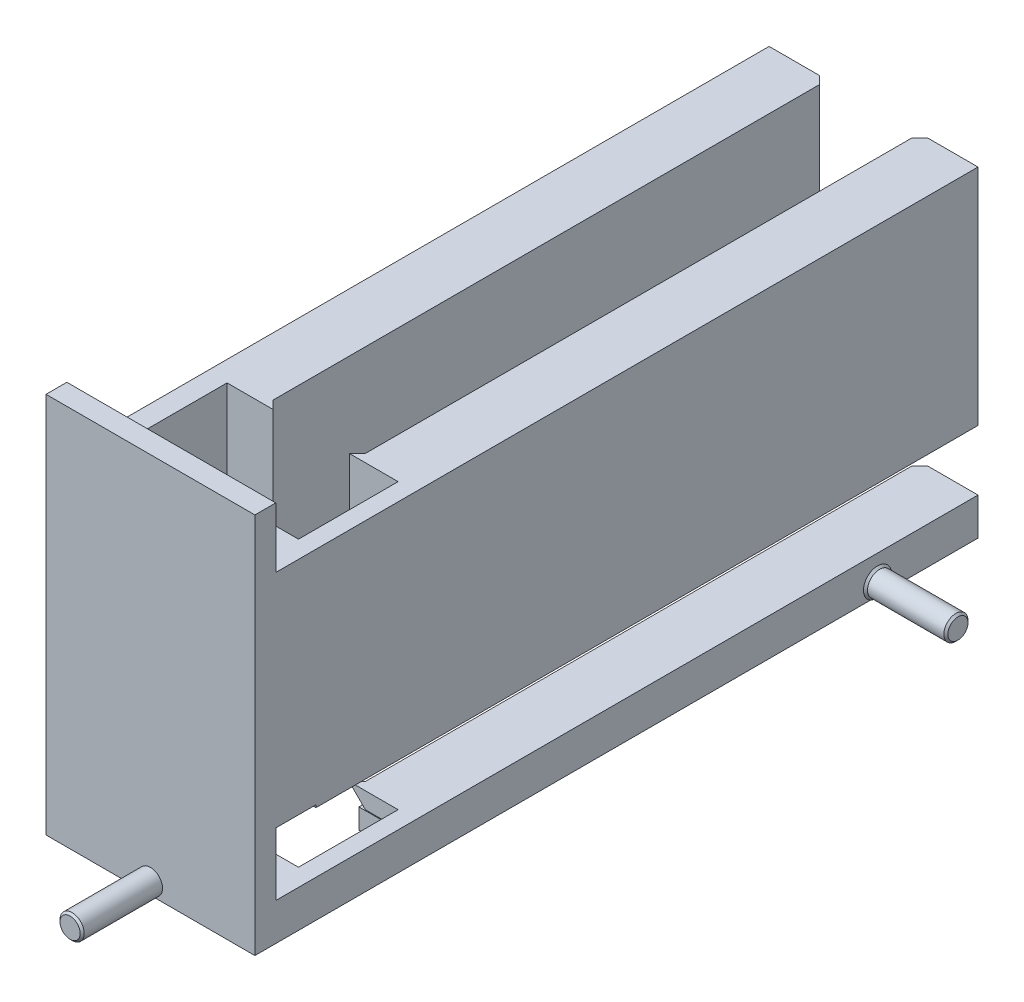
SolidWorks part; units mm, degrees
ref_plane "前视基准面" through (0, 0, 0) normal (0, 0, 1) x (1, 0, 0)
ref_plane "上视基准面" through (0, 0, 0) normal (0, 1, 0) x (1, 0, 0)
ref_plane "右视基准面" through (0, 0, 0) normal (1, 0, 0) x (0, 0, -1)
sketch "草图1" plane through (0, 0, 0) normal (0, 0, 1) x (1, 0, 0)
  line L0 (0, 0) -> (0, 95) construction
  line L1 (-21, 0) -> (21, 0) construction
  line L2 (21, 0) -> (21, 95) construction
  line L3 (21, 95) -> (-21, 95) construction
  line L4 (-21, 0) -> (-21, 95) construction
  line L5 (-26, 0) -> (26, 0)
  line L6 (26, 0) -> (26, 95)
  line L7 (26, 95) -> (-26, 95)
  line L8 (-26, 0) -> (-26, 95)
extrude "凸台-拉伸1" add sketch "草图1" along normal blind 180
sketch "草图2" plane through (0, 0, 0) normal (0, 0, -1) x (-1, 0, 0)
  line L0 (0, 0) -> (0, 5) construction
  line L1 (0, 0) -> (0, 95) construction
  line L2 (-11.5, 5) -> (11.5, 5)
  line L3 (11.5, 5) -> (11.5, 95)
  line L4 (-26, 95) -> (26, 95) construction
  line L5 (11.5, 95) -> (-11.5, 95)
  line L6 (0, 95) -> (0, 5) construction
  line L7 (-11.5, 5) -> (-11.5, 95)
extrude "切除-拉伸1" cut sketch "草图2" against normal blind 140
sketch "草图3" plane through (0, 0, 0) normal (0, 0, -1) x (-1, 0, 0)
  line L0 (-11.5, 5) -> (-11.5, 7.2) construction
  line L1 (-11.5, 95) -> (-11.5, 5) construction
  line L2 (-11.5, 7.2) -> (-21, 7.2)
  line L3 (-21, 0) -> (-21, 95) construction
  line L4 (-21, 7.2) -> (-21, 5)
  line L5 (-21, 5) -> (-11.5, 5)
  line L6 (-11.5, 5) -> (-11.5, 7.2)
  line L7 (0, 0) -> (0, 12.5815) construction
  line L8 (26, 0) -> (-26, 0) construction
  line L9 (0, 0) -> (0, 95) construction
  line L10 (11.5, 5) -> (11.5, 7.2) construction
  line L11 (11.5, 5) -> (11.5, 7.2)
  line L12 (21, 5) -> (11.5, 5)
  line L13 (21, 7.2) -> (21, 5)
  line L14 (11.5, 7.2) -> (21, 7.2)
extrude "切除-拉伸2" cut sketch "草图3" against normal blind 140
chamfer "倒角1" distance 2 angle 45 11 edges at (0, 95, 140) (16.25, 7.2, 140) (11.5, 95, 70) (11.5, 51.1, 0) (11.5, 51.1, 140) (11.5, 7.2, 70) (-16.25, 7.2, 140) (-11.5, 95, 70) (-11.5, 51.1, 0) (-11.5, 7.2, 70) (-11.5, 51.1, 140)
sketch "草图4" plane through (0, 0, 0) normal (0, 0, -1) x (-1, 0, 0)
  line L0 (0, 0) -> (-11.8737, 0)
  line L1 (26, 0) -> (-26, 0) construction
  line L2 (-11.8737, 0) -> (-11.8737, 5)
  line L3 (-21, 5) -> (21, 5) construction
  line L4 (-11.8737, 5) -> (12.1263, 5)
  line L5 (-21, 5) -> (21, 5) construction
  line L6 (12.1263, 5) -> (12.1263, 0)
  line L7 (12.1263, 0) -> (-0.5655, 0)
  line M7 (21, 5) -> (-21, 5)
  line M13 (-26, 0) -> (26, 0)
extrude "切除-拉伸3" cut sketch "草图4" against normal blind 140 contours L6 L2 L0 M7 M13
sketch "草图5" plane through (26, 0, 0) normal (1, 0, 0) x (0, 0, -1)
  line L1 (0, 95) -> (-140, 95)
  line L2 (0, 95) -> (0, 80)
  line L3 (0, 80) -> (-140, 80)
  line L4 (-140, 95) -> (-140, 80)
extrude "切除-拉伸4" cut sketch "草图5" against normal blind 140
sketch "草图6" plane through (26, 0, 0) normal (1, 0, 0) x (0, 0, -1)
  line L0 (0, 0) -> (0, 95) construction
  line L1 (0, 9.2842) -> (-140, 9.2842)
  line L2 (0, 9.2842) -> (0, 24.2842)
  line L3 (0, 24.2842) -> (-140, 24.2842)
  line L4 (-140, 9.2842) -> (-140, 24.2842)
  line L5 (0, 24.2842) -> (-15, 24.2842) construction
extrude "切除-拉伸7" cut sketch "草图6" against normal blind 140
sketch "草图7" plane through (0, 95, 0) normal (0, 1, 0) x (1, 0, 0)
  line L0 (0, -140) -> (0, -164.8085) construction
  line L1 (-9.5, -140) -> (9.5, -140) construction
  line L2 (0, -140) -> (21.6541, -140)
  line L3 (11.5, -140) -> (26, -140) construction
  line L4 (21.6541, -140) -> (21.6541, -164.8085)
  line L5 (21.6541, -164.8085) -> (-20.3459, -164.8085)
  line L6 (-20.9264, -140) -> (-20.9264, -164.8085)
  line L7 (-26, -140) -> (-9.5, -140) construction
  line L8 (-20.9264, -164.8085) -> (-20.3459, -164.8085)
  line L9 (-20.9264, -140) -> (0, -140)
extrude "切除-拉伸8" cut sketch "草图7" against normal blind 140
sketch "草图8" plane through (26, 0, 0) normal (1, 0, 0) x (0, 0, -1)
  line L1 (-140, 80) -> (-164.8085, 80)
  line L2 (-140, 80) -> (-140, 95)
  line L3 (-140, 95) -> (-164.8085, 95)
  line L4 (-164.8085, 80) -> (-164.8085, 95)
  line L5 (-140, 9.2842) -> (-164.8085, 9.2842)
  line L6 (-140, 9.2842) -> (-140, 24.2842)
  line L7 (-140, 24.2842) -> (-164.8085, 24.2842)
  line L8 (-164.8085, 9.2842) -> (-164.8085, 24.2842)
extrude "切除-拉伸9" cut sketch "草图8" against normal blind 140
sketch "草图9" plane through (26, 0, 0) normal (1, 0, 0) x (0, 0, -1)
  line L0 (-164.8085, 95) -> (-164.8085, 80) construction
  line L1 (-164.8085, 80.8239) -> (-174.8085, 80.8239)
  line L2 (-164.8085, 80.8239) -> (-164.8085, 95)
  line L3 (-164.8085, 95) -> (-174.8085, 95)
  line L4 (-174.8085, 80.8239) -> (-174.8085, 95)
  line L5 (-180, 95) -> (-164.8085, 95) construction
  line L7 (-164.8085, 9.2842) -> (-174.8085, 9.2842)
  line L8 (-164.8085, 9.2842) -> (-164.8085, 24.915)
  line L9 (-164.8085, 24.915) -> (-174.8085, 24.915)
  line L10 (-174.8085, 9.2842) -> (-174.8085, 24.915)
extrude "切除-拉伸10" cut sketch "草图9" against normal blind 140
sketch "草图10" plane through (0, 0, 164.8085) normal (0, 0, -1) x (-1, 0, 0)
  line L0 (-26, 80.8239) -> (-26, 80)
  line L1 (-26, 80) -> (26, 80)
  line L2 (26, 80) -> (26, 80.8239)
  line L3 (26, 80.8239) -> (-26, 80.8239)
extrude "切除-拉伸11" cut sketch "草图10" against normal blind 10
sketch "草图12" plane through (0, 0, 180) normal (0, 0, 1) x (1, 0, 0)
  line L0 (0, 0) -> (0, 3.01) construction
  line L1 (0, 0) -> (0, 95) construction
  circle A0 centre (0, 3.01) radius 3.01
extrude "凸台-拉伸2" add sketch "草图12" along normal blind 20
chamfer "倒角3" distance 0.5 angle 45 1 edges at (3.01, 3.01, 200)
sketch "草图13" plane through (26, 0, 0) normal (1, 0, 0) x (0, 0, -1)
  line L0 (0, 0) -> (-25, 0) construction
  line L1 (-180, 0) -> (0, 0) construction
  line L2 (-25, 0) -> (-25, 3.01) construction
  circle A0 centre (-25, 3.01) radius 3.01
extrude "凸台-拉伸4" add sketch "草图13" along normal blind 20
chamfer "倒角4" distance 0.5 angle 45 2 edges at (26, 3.01, 21.99) (46, 3.01, 21.99)
sketch "草图15" plane through (-26, 0, 0) normal (-1, 0, 0) x (0, 0, 1)
  line L0 (0, 0) -> (25, 0) construction
  line L1 (180, 0) -> (0, 0) construction
  line L2 (25, 0) -> (25, 3.01) construction
  circle A0 centre (25, 3.01) radius 3.01
extrude "凸台-拉伸5" add sketch "草图15" along normal blind 20
chamfer "倒角5" distance 0.5 angle 45 2 edges at (-26, 3.01, 28.01) (-46, 3.01, 28.01)
